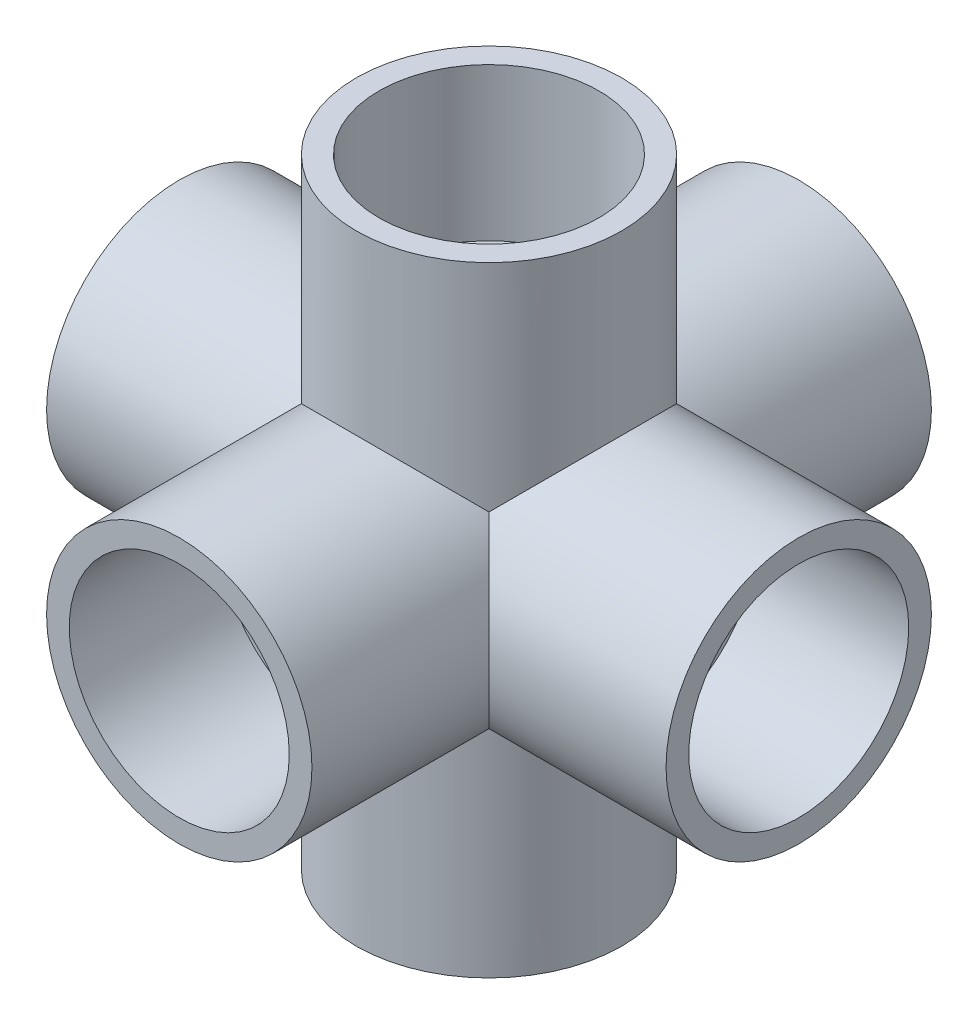
SolidWorks part; units mm, degrees
ref_plane "前视基准面" through (0, 0, 0) normal (0, 0, 1) x (1, 0, 0)
ref_plane "上视基准面" through (0, 0, 0) normal (0, 1, 0) x (1, 0, 0)
ref_plane "右视基准面" through (0, 0, 0) normal (1, 0, 0) x (0, 0, -1)
other "Configuration Table"
sketch "草图1" plane through (0, 0, 0) normal (0, 1, 0) x (1, 0, 0)
  circle A14 centre (0, 0) radius 19.3
  circle A15 centre (0, 0) radius 16
  circle A16 centre (0, 0) radius 13.6
  dimension "D3" = 2.4
  dimension "D1" = 32
  dimension "D2" = 3.3
extrude "凸台-拉伸1" add sketch "草图1" along normal mid plane 90.1 contours A14 | A16
sketch "草图3" plane through (0, 0, 0) normal (1, 0, 0) x (0, 0, -1)
  circle A0 centre (0, 0) radius 19.3
  circle A1 centre (0, 0) radius 16
  circle A2 centre (0, 0) radius 13.6
  dimension "D1" = 3.3
  dimension "D2" = 32
  dimension "D3" = 2.4
extrude "凸台-拉伸3" add sketch "草图3" along normal mid plane 90.1 contours A0 | A2
sketch "草图2" plane through (0, 0, 0) normal (0, 0, 1) x (1, 0, 0)
  circle A0 centre (0, 0) radius 16
  circle A1 centre (0, 0) radius 19.3
  circle A2 centre (0, 0) radius 13.6
  dimension "D1" = 32
  dimension "D2" = 3.3
  dimension "D3" = 2.4
extrude "凸台-拉伸2" add sketch "草图2" along normal mid plane 90.1 contours A1 | A2
extrude "切除-拉伸1" cut sketch "草图1<13>" against normal through all both and the other way through all contours A16
sketch "草图1<13>" plane through (0, 0, 0) normal (0, 1, 0) x (1, 0, 0) same geometry as "草图1"
extrude "切除-拉伸2" cut sketch "草图3<8>" against normal through all both and the other way through all contours A2
sketch "草图3<8>" plane through (0, 0, 0) normal (1, 0, 0) x (0, 0, -1) same geometry as "草图3"
extrude "切除-拉伸3" cut sketch "草图2<8>" against normal through all both and the other way through all from surface contours A2 starting at face at (19.3, 0, 45.05)
sketch "草图2<8>" plane through (0, 0, 0) normal (0, 0, 1) x (1, 0, 0) same geometry as "草图2"
extrude "切除-拉伸4" cut sketch "草图1<15>" along normal blind 22.2 from surface contours A15 starting at face at (0, -45.05, 19.3)
sketch "草图1<15>" plane through (0, 0, 0) normal (0, 1, 0) x (1, 0, 0) same geometry as "草图1"
extrude "切除-拉伸5" cut sketch "草图1<16>" against normal blind 22.2 from surface contours A15 starting at face at (0, 45.05, 19.3)
sketch "草图1<16>" plane through (0, 0, 0) normal (0, 1, 0) x (1, 0, 0) same geometry as "草图1"
extrude "切除-拉伸6" cut sketch "草图3<9>" along normal blind 22.2 from surface contours A1 starting at face at (-45.05, 0, -19.3)
sketch "草图3<9>" plane through (0, 0, 0) normal (1, 0, 0) x (0, 0, -1) same geometry as "草图3"
extrude "切除-拉伸7" cut sketch "草图3<10>" against normal blind 22.2 from surface contours A1 starting at face at (45.05, 0, -19.3)
sketch "草图3<10>" plane through (0, 0, 0) normal (1, 0, 0) x (0, 0, -1) same geometry as "草图3"
extrude "切除-拉伸8" cut sketch "草图2<9>" against normal blind 22.2 from surface contours A0 starting at face at (19.3, 0, 45.05)
sketch "草图2<9>" plane through (0, 0, 0) normal (0, 0, 1) x (1, 0, 0) same geometry as "草图2"
